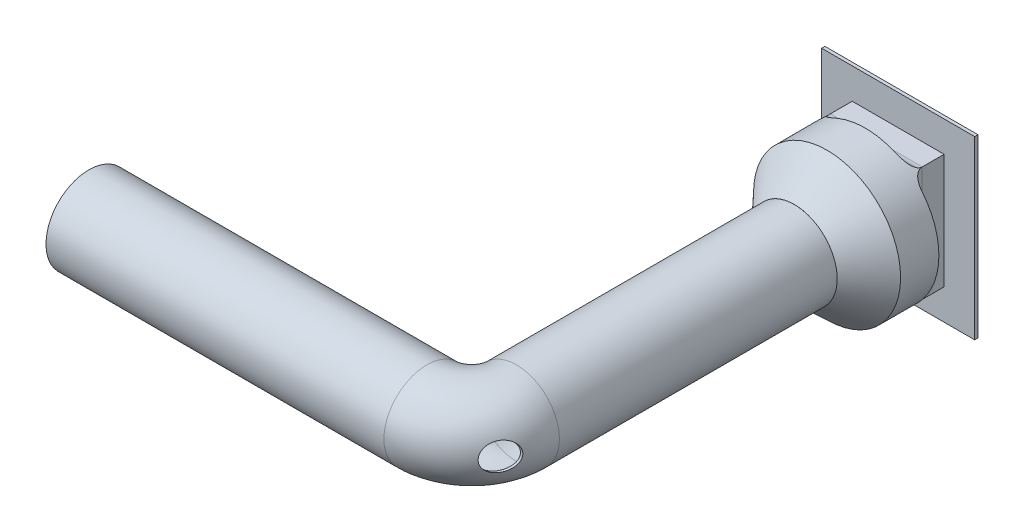
SolidWorks part; units mm, degrees
ref_plane "Alzado" through (0, 0, 0) normal (0, 0, 1) x (1, 0, 0)
ref_plane "Planta" through (0, 0, 0) normal (0, 1, 0) x (1, 0, 0)
ref_plane "Vista lateral" through (0, 0, 0) normal (1, 0, 0) x (0, 0, -1)
sketch "Croquis1" plane through (0, 0, 0) normal (0, 0, 1) x (1, 0, 0)
  line L0 (30, -30) -> (110, -30)
  line L1 (0, 0) -> (140, 0)
  line L2 (0, 0) -> (0, -161)
  line L3 (0, -161) -> (140, -161)
  line L4 (140, 0) -> (140, -161)
  line L5 (110, -30) -> (110, -131)
  line L6 (30, -131) -> (110, -131)
  line L7 (30, -30) -> (30, -131)
  dimension "D1" = 161
  dimension "D2" = 140
  dimension "D3" = 30
extrude "Saliente-Extruir1" add sketch "Croquis1" along normal blind 3
sketch "Croquis2" plane through (0, 0, 3) normal (0, 0, 1) x (1, 0, 0)
  line L0 (28, -133) -> (28, -28)
  line L1 (30, -131) -> (110, -131)
  line L2 (30, -131) -> (30, -30)
  line L3 (30, -30) -> (110, -30)
  line L4 (110, -131) -> (110, -30)
  line L5 (28, -28) -> (112, -28)
  line L6 (112, -133) -> (112, -28)
  line L7 (28, -133) -> (112, -133)
  dimension "D1" = 2
extrude "Saliente-Extruir2" add sketch "Croquis2" along normal blind 30
sketch "Croquis3" plane through (0, 0, 33) normal (0, 0, 1) x (1, 0, 0)
  line L0 (70, -30) -> (70, -131) construction
  line L1 (110, -30) -> (30, -30) construction
  line L2 (30, -131) -> (110, -131) construction
  circle A0 centre (70, -80.5) radius 67.2328
  circle A1 centre (70, -80.5) radius 39.2328
  dimension "D1" = 28
extrude "Saliente-Extruir3" add sketch "Croquis3" along normal blind 65
sketch "Croquis6" plane through (0, 0, 98) normal (0, 0, 1) x (1, 0, 0)
  circle A0 centre (70, -80.5) radius 39.2328
  circle A1 centre (70, -80.5) radius 37.2328
  dimension "D1" = 2
extrude "Saliente-Extruir4" add sketch "Croquis6" along normal blind 45 separate body
chamfer "Chaflán1" distance 30 angle 43 1 edges at (137.2328, -80.5, 98) first distance on face at (137.2328, -80.5, 98)
fillet "Redondeo1" radius 10 1 edges at (70, -28, 33)
fillet "Redondeo2" radius 10 1 edges at (112, -80.5, 33)
fillet "Redondeo3" radius 10 1 edges at (28, -80.5, 33)
fillet "Redondeo4" radius 10 1 edges at (70, -133, 33)
sketch3d "Croquis3D1"
  line L0 (70, -80.5, 143) -> (70, -80.5, 352)
  line L1 (70, -80.5, 143) -> (70, -80.5, 98) construction
  line L2 (29, -80.5, 393) -> (-280, -80.5, 393)
  arc A0 (70, -80.5, 352) -> (29, -80.5, 393) centre (29, -80.5, 352) ccw
  point P7 (70, -80.5, 393)
  point P8 (29, -121.5, 352)
  dimension "D3" = 41
  dimension "D1" = 250
  dimension "D2" = 350
sketch "Croquis7" plane through (0, 0, 143) normal (0, 0, 1) x (1, 0, 0)
  circle A0 centre (70, -80.5) radius 37.2328
  circle A1 centre (70, -80.5) radius 39.2328
sweep "Barrer1" add profiles "Croquis7" path "Croquis3D1"
sketch "Croquis8" plane through (0, 0, 0) normal (1, 0, 0) x (0, 0, -1)
  circle A0 centre (-393, -80.5) radius 39.2328 construction
  circle A1 centre (-393, -80.5) radius 12.7
  dimension "D1" = 25.4
extrude "Cortar-Extruir1" cut sketch "Croquis8" along normal blind 120
